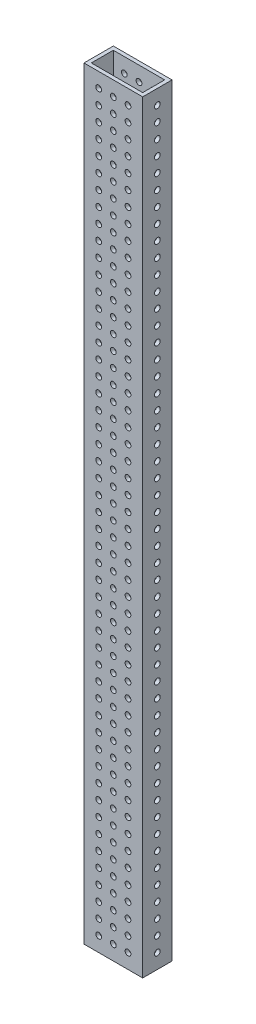
SolidWorks part; units mm, degrees
ref_plane "Front Plane" through (0, 0, 0) normal (0, 0, 1) x (1, 0, 0)
ref_plane "Top Plane" through (0, 0, 0) normal (0, 1, 0) x (1, 0, 0)
ref_plane "Right Plane" through (0, 0, 0) normal (1, 0, 0) x (0, 0, -1)
sketch "Sketch1" plane through (0, 0, 0) normal (0, 1, 0) x (1, 0, 0)
  line L0 (3.175, 22.225) -> (47.625, 22.225)
  line L1 (0, 0) -> (50.8, 0)
  line L2 (0, 0) -> (0, 25.4)
  line L3 (0, 25.4) -> (50.8, 25.4)
  line L4 (50.8, 0) -> (50.8, 25.4)
  line L5 (47.625, 3.175) -> (47.625, 22.225)
  line L6 (3.175, 3.175) -> (47.625, 3.175)
  line L7 (3.175, 3.175) -> (3.175, 22.225)
  dimension "D1" = 50.8
  dimension "D2" = 25.4
  dimension "D3" = 3.175
extrude "Boss-Extrude1" add sketch "Sketch1" along normal mid plane 660.4
sketch "Sketch2" plane through (0, 0, 0) normal (0, 0, 1) x (1, 0, 0)
  line L2 (0, 330.2) -> (50.8, 330.2) construction
  line L3 (0, 330.2) -> (0, -330.2) construction
  circle A291 centre (12.7, 317.5) radius 2.4892
  dimension "D1" = 12.7
  dimension "D2" = 12.7
  dimension "D3" = 4.9784
extrude "Cut-Extrude1" cut sketch "Sketch2" against normal through all
pattern_linear "LPattern1" count 51 spacing 12.7 along (0, -1, 0) count 3 spacing 12.7 along (1, 0, 0) of "Cut-Extrude1"
sketch "Sketch3" plane through (50.8, 0, 0) normal (1, 0, 0) x (0, 0, -1)
  line L0 (0, 330.2) -> (0, -330.2) construction
  line L1 (0, 330.2) -> (25.4, 330.2) construction
  circle A0 centre (12.7, 317.5) radius 2.4892
  dimension "D1" = 4.9784
  dimension "D2" = 12.7
  dimension "D3" = 12.7
extrude "Cut-Extrude2" cut sketch "Sketch3" against normal up to next
pattern_linear "LPattern2" count 51 spacing 12.7 along (0, -1, 0) of "Cut-Extrude2"
